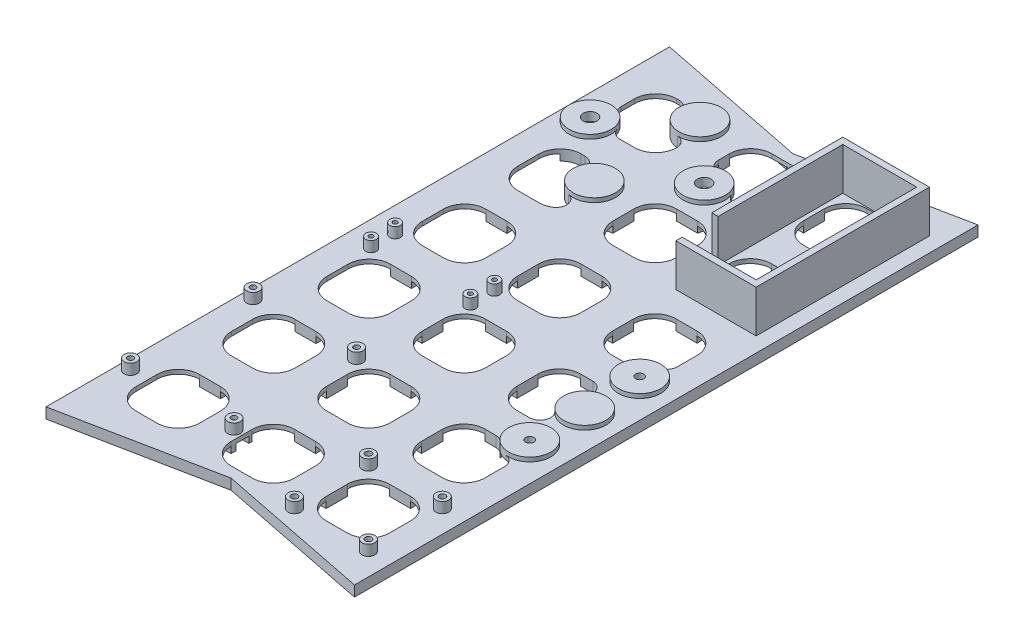
SolidWorks part; units mm, degrees
ref_plane "Front Plane" through (0, 0, 0) normal (0, 0, 1) x (1, 0, 0)
ref_plane "Top Plane" through (0, 0, 0) normal (0, 1, 0) x (1, 0, 0)
ref_plane "Right Plane" through (0, 0, 0) normal (1, 0, 0) x (0, 0, -1)
ref_axis "X" through (-88.99, 0, 0) along (1, 0, 0)
ref_axis "Y" through (0, 55, 0) along (0, -1, 0)
ref_axis "Z" through (0, 0, -88.99) along (0, 0, 1)
sketch "Sketch1" plane through (0, 0, 0) normal (0, 1, 0) x (1, 0, 0)
  line L0 (-75, 150) -> (0, 135) construction
  line L1 (-75, 150) -> (75, 150) construction
  line L2 (-75, 150) -> (-75, -150) construction
  line L3 (-75, -150) -> (75, -150) construction
  line L4 (75, 150) -> (75, -150) construction
  line L5 (-75, 150) -> (75, -150) construction
  line L6 (-75, -150) -> (75, 150) construction
  line L7 (0, 135) -> (75, 150) construction
  line L8 (-75, 0) -> (75, 0) construction
  line L9 (-75, -150) -> (0, -135) construction
  line L10 (0, -135) -> (75, -150) construction
  line L11 (-73, 147.5604) -> (-73, -147.5604)
  line L12 (-73, -147.5604) -> (0, -132.9604)
  line L13 (0, -132.9604) -> (73, -147.5604)
  line L14 (73, 147.5604) -> (73, -147.5604)
  line L15 (0, 132.9604) -> (73, 147.5604)
  line L16 (-73, 147.5604) -> (0, 132.9604)
  point P0 (0, 0)
  dimension "D1" = 300
  dimension "D2" = 150
  dimension "D3" = 15
  dimension "D4" = 2
extrude "Boss-Extrude1" add sketch "Sketch1" along normal blind 2
sketch "Sketch2" plane through (0, 2, 0) normal (0, 1, 0) x (1, 0, 0)
  line L0 (-73, 147.5604) -> (-73, -147.5604) construction
  line L1 (-50, -127.9604) -> (-40, -127.9604)
  line L2 (-60, -117.9604) -> (-60, -107.9604)
  line L3 (-50, -97.9604) -> (-40, -97.9604)
  line L4 (-30, -117.9604) -> (-30, -107.9604)
  line L5 (-15, -117.9604) -> (-15, -107.9604)
  line L6 (-5, -127.9604) -> (5, -127.9604)
  line L7 (15, -117.9604) -> (15, -107.9604)
  line L8 (-5, -97.9604) -> (5, -97.9604)
  line L9 (30, -117.9604) -> (30, -107.9604)
  line L10 (40, -127.9604) -> (50, -127.9604)
  line L11 (60, -117.9604) -> (60, -107.9604)
  line L12 (40, -97.9604) -> (50, -97.9604)
  line L73 (-60, -72.7762) -> (-60, -62.7762)
  line L74 (-50, -82.7762) -> (-40, -82.7762)
  line L75 (-30, -72.7762) -> (-30, -62.7762)
  line L76 (-50, -52.7762) -> (-40, -52.7762)
  line L77 (-15, -72.7762) -> (-15, -62.7762)
  line L78 (-5, -52.7762) -> (5, -52.7762)
  line L79 (15, -72.7762) -> (15, -62.7762)
  line L80 (-5, -82.7762) -> (5, -82.7762)
  line L81 (30, -72.7762) -> (30, -62.7762)
  line L82 (40, -52.7762) -> (50, -52.7762)
  line L83 (60, -72.7762) -> (60, -62.7762)
  line L84 (40, -82.7762) -> (50, -82.7762)
  line L85 (-60, -27.5921) -> (-60, -17.5921)
  line L86 (-50, -37.5921) -> (-40, -37.5921)
  line L87 (-30, -27.5921) -> (-30, -17.5921)
  line L88 (-50, -7.5921) -> (-40, -7.5921)
  line L89 (-15, -27.5921) -> (-15, -17.5921)
  line L90 (-5, -7.5921) -> (5, -7.5921)
  line L91 (15, -27.5921) -> (15, -17.5921)
  line L92 (-5, -37.5921) -> (5, -37.5921)
  line L93 (30, -27.5921) -> (30, -17.5921)
  line L94 (40, -7.5921) -> (50, -7.5921)
  line L95 (60, -27.5921) -> (60, -17.5921)
  line L96 (40, -37.5921) -> (50, -37.5921)
  line L97 (-60, 17.5921) -> (-60, 27.5921)
  line L98 (-50, 7.5921) -> (-40, 7.5921)
  line L99 (-30, 17.5921) -> (-30, 27.5921)
  line L100 (-50, 37.5921) -> (-40, 37.5921)
  line L101 (-15, 17.5921) -> (-15, 27.5921)
  line L102 (-5, 37.5921) -> (5, 37.5921)
  line L103 (15, 17.5921) -> (15, 27.5921)
  line L104 (-5, 7.5921) -> (5, 7.5921)
  line L105 (30, 17.5921) -> (30, 27.5921)
  line L106 (40, 37.5921) -> (50, 37.5921)
  line L107 (60, 17.5921) -> (60, 27.5921)
  line L108 (40, 7.5921) -> (50, 7.5921)
  line L109 (-60, 62.7762) -> (-60, 72.7762)
  line L110 (-50, 52.7762) -> (-40, 52.7762)
  line L111 (-30, 62.7762) -> (-30, 72.7762)
  line L112 (-50, 82.7762) -> (-40, 82.7762)
  line L113 (-15, 62.7762) -> (-15, 72.7762)
  line L114 (-5, 82.7762) -> (5, 82.7762)
  line L115 (15, 62.7762) -> (15, 72.7762)
  line L116 (-5, 52.7762) -> (5, 52.7762)
  line L117 (30, 62.7762) -> (30, 72.7762)
  line L118 (40, 82.7762) -> (50, 82.7762)
  line L119 (60, 62.7762) -> (60, 72.7762)
  line L120 (40, 52.7762) -> (50, 52.7762)
  line L121 (-60, 107.9604) -> (-60, 117.9604)
  line L122 (-50, 97.9604) -> (-40, 97.9604)
  line L123 (-30, 107.9604) -> (-30, 117.9604)
  line L124 (-50, 127.9604) -> (-40, 127.9604)
  line L125 (-15, 107.9604) -> (-15, 117.9604)
  line L126 (-5, 127.9604) -> (5, 127.9604)
  line L127 (15, 107.9604) -> (15, 117.9604)
  line L128 (-5, 97.9604) -> (5, 97.9604)
  line L129 (30, 107.9604) -> (30, 117.9604)
  line L130 (40, 127.9604) -> (50, 127.9604)
  line L131 (60, 107.9604) -> (60, 117.9604)
  line L132 (40, 97.9604) -> (50, 97.9604)
  arc A0 (-60, -117.9604) -> (-50, -127.9604) centre (-50, -117.9604) ccw
  arc A1 (-40, -127.9604) -> (-30, -117.9604) centre (-40, -117.9604) ccw
  arc A2 (-30, -107.9604) -> (-40, -97.9604) centre (-40, -107.9604) ccw
  arc A3 (-50, -97.9604) -> (-60, -107.9604) centre (-50, -107.9604) ccw
  arc A4 (60, -107.9604) -> (50, -97.9604) centre (50, -107.9604) ccw
  arc A5 (50, -127.9604) -> (60, -117.9604) centre (50, -117.9604) ccw
  arc A6 (40, -127.9604) -> (30, -117.9604) centre (40, -117.9604) cw
  arc A7 (30, -107.9604) -> (40, -97.9604) centre (40, -107.9604) cw
  arc A8 (-15, -107.9604) -> (-5, -97.9604) centre (-5, -107.9604) cw
  arc A9 (-15, -117.9604) -> (-5, -127.9604) centre (-5, -117.9604) ccw
  arc A10 (15, -117.9604) -> (5, -127.9604) centre (5, -117.9604) cw
  arc A11 (15, -107.9604) -> (5, -97.9604) centre (5, -107.9604) ccw
  arc A12 (-50, -52.7762) -> (-60, -62.7762) centre (-50, -62.7762) ccw
  arc A13 (-60, -72.7762) -> (-50, -82.7762) centre (-50, -72.7762) ccw
  arc A14 (-40, -82.7762) -> (-30, -72.7762) centre (-40, -72.7762) ccw
  arc A15 (-30, -62.7762) -> (-40, -52.7762) centre (-40, -62.7762) ccw
  arc A16 (-15, -72.7762) -> (-5, -82.7762) centre (-5, -72.7762) ccw
  arc A17 (-15, -62.7762) -> (-5, -52.7762) centre (-5, -62.7762) cw
  arc A18 (15, -62.7762) -> (5, -52.7762) centre (5, -62.7762) ccw
  arc A19 (15, -72.7762) -> (5, -82.7762) centre (5, -72.7762) cw
  arc A20 (30, -62.7762) -> (40, -52.7762) centre (40, -62.7762) cw
  arc A21 (40, -82.7762) -> (30, -72.7762) centre (40, -72.7762) cw
  arc A22 (60, -62.7762) -> (50, -52.7762) centre (50, -62.7762) ccw
  arc A23 (50, -82.7762) -> (60, -72.7762) centre (50, -72.7762) ccw
  arc A24 (-50, -7.5921) -> (-60, -17.5921) centre (-50, -17.5921) ccw
  arc A25 (-60, -27.5921) -> (-50, -37.5921) centre (-50, -27.5921) ccw
  arc A26 (-40, -37.5921) -> (-30, -27.5921) centre (-40, -27.5921) ccw
  arc A27 (-30, -17.5921) -> (-40, -7.5921) centre (-40, -17.5921) ccw
  arc A28 (-15, -27.5921) -> (-5, -37.5921) centre (-5, -27.5921) ccw
  arc A29 (-15, -17.5921) -> (-5, -7.5921) centre (-5, -17.5921) cw
  arc A30 (15, -17.5921) -> (5, -7.5921) centre (5, -17.5921) ccw
  arc A31 (15, -27.5921) -> (5, -37.5921) centre (5, -27.5921) cw
  arc A32 (30, -17.5921) -> (40, -7.5921) centre (40, -17.5921) cw
  arc A33 (40, -37.5921) -> (30, -27.5921) centre (40, -27.5921) cw
  arc A34 (60, -17.5921) -> (50, -7.5921) centre (50, -17.5921) ccw
  arc A35 (50, -37.5921) -> (60, -27.5921) centre (50, -27.5921) ccw
  arc A36 (-50, 37.5921) -> (-60, 27.5921) centre (-50, 27.5921) ccw
  arc A37 (-60, 17.5921) -> (-50, 7.5921) centre (-50, 17.5921) ccw
  arc A38 (-40, 7.5921) -> (-30, 17.5921) centre (-40, 17.5921) ccw
  arc A39 (-30, 27.5921) -> (-40, 37.5921) centre (-40, 27.5921) ccw
  arc A40 (-15, 17.5921) -> (-5, 7.5921) centre (-5, 17.5921) ccw
  arc A41 (-15, 27.5921) -> (-5, 37.5921) centre (-5, 27.5921) cw
  arc A42 (15, 27.5921) -> (5, 37.5921) centre (5, 27.5921) ccw
  arc A43 (15, 17.5921) -> (5, 7.5921) centre (5, 17.5921) cw
  arc A44 (30, 27.5921) -> (40, 37.5921) centre (40, 27.5921) cw
  arc A45 (40, 7.5921) -> (30, 17.5921) centre (40, 17.5921) cw
  arc A46 (60, 27.5921) -> (50, 37.5921) centre (50, 27.5921) ccw
  arc A47 (50, 7.5921) -> (60, 17.5921) centre (50, 17.5921) ccw
  arc A48 (-50, 82.7762) -> (-60, 72.7762) centre (-50, 72.7762) ccw
  arc A49 (-60, 62.7762) -> (-50, 52.7762) centre (-50, 62.7762) ccw
  arc A50 (-40, 52.7762) -> (-30, 62.7762) centre (-40, 62.7762) ccw
  arc A51 (-30, 72.7762) -> (-40, 82.7762) centre (-40, 72.7762) ccw
  arc A52 (-15, 62.7762) -> (-5, 52.7762) centre (-5, 62.7762) ccw
  arc A53 (-15, 72.7762) -> (-5, 82.7762) centre (-5, 72.7762) cw
  arc A54 (15, 72.7762) -> (5, 82.7762) centre (5, 72.7762) ccw
  arc A55 (15, 62.7762) -> (5, 52.7762) centre (5, 62.7762) cw
  arc A56 (30, 72.7762) -> (40, 82.7762) centre (40, 72.7762) cw
  arc A57 (40, 52.7762) -> (30, 62.7762) centre (40, 62.7762) cw
  arc A58 (60, 72.7762) -> (50, 82.7762) centre (50, 72.7762) ccw
  arc A59 (50, 52.7762) -> (60, 62.7762) centre (50, 62.7762) ccw
  arc A60 (-50, 127.9604) -> (-60, 117.9604) centre (-50, 117.9604) ccw
  arc A61 (-60, 107.9604) -> (-50, 97.9604) centre (-50, 107.9604) ccw
  arc A62 (-40, 97.9604) -> (-30, 107.9604) centre (-40, 107.9604) ccw
  arc A63 (-30, 117.9604) -> (-40, 127.9604) centre (-40, 117.9604) ccw
  arc A64 (-15, 107.9604) -> (-5, 97.9604) centre (-5, 107.9604) ccw
  arc A65 (-15, 117.9604) -> (-5, 127.9604) centre (-5, 117.9604) cw
  arc A66 (15, 117.9604) -> (5, 127.9604) centre (5, 117.9604) ccw
  arc A67 (15, 107.9604) -> (5, 97.9604) centre (5, 107.9604) cw
  arc A68 (30, 117.9604) -> (40, 127.9604) centre (40, 117.9604) cw
  arc A69 (40, 97.9604) -> (30, 107.9604) centre (40, 107.9604) cw
  arc A70 (60, 117.9604) -> (50, 127.9604) centre (50, 117.9604) ccw
  arc A71 (50, 97.9604) -> (60, 107.9604) centre (50, 107.9604) ccw
  point P81 (-30, -127.9604)
  point P84 (-30, -97.9604)
  point P87 (-60, -97.9604)
  dimension "D9" = 10
  dimension "D7" = 10
  dimension "D1" = 30
  dimension "D2" = 30
  dimension "D3" = 13
  dimension "D4" = 5
  dimension "D6" = 15
  dimension "D8" = 6
  dimension "D10" = 5
  dimension "D5" = 3
extrude "Cut-Extrude1" cut sketch "Sketch2" against normal through all
sketch "Sketch3" plane through (0, 2, 0) normal (0, 1, 0) x (1, 0, 0)
  line L1 (-73, 147.5604) -> (-73, -147.5604) construction
  circle A0 centre (-68, -54.5604) radius 3
  circle A1 centre (-19, -54.5604) radius 3
  circle A2 centre (-68, -112.5604) radius 3
  circle A3 centre (-19, -112.5604) radius 3
  dimension "D1" = 6
  dimension "D2" = 49
  dimension "D3" = 58
  dimension "D4" = 5
  dimension "D5" = 35
extrude "Boss-Extrude2" add sketch "Sketch3" along normal blind 5 and the other way through all
sketch "Sketch4" plane through (0, 7, 0) normal (0, 1, 0) x (1, 0, 0)
  circle A1 centre (-19, -112.5604) radius 1.35
  circle A2 centre (-68, -112.5604) radius 1.35
  circle A3 centre (-68, -54.5604) radius 1.35
  circle A4 centre (-19, -54.5604) radius 1.35
  dimension "D1" = 2.7
extrude "Cut-Extrude2" cut sketch "Sketch4" against normal through all
sketch "Sketch5" plane through (0, 2, 0) normal (0, 1, 0) x (1, 0, 0)
  line L0 (30, -112.9604) -> (60, -112.9604) construction
  line L1 (30, -107.9604) -> (30, -117.9604) construction
  line L2 (60, -117.9604) -> (60, -107.9604) construction
  circle A0 centre (27.5, -95.4604) radius 3
  circle A2 centre (62.5, -95.4604) radius 3
  circle A4 centre (62.5, -130.4604) radius 3
  circle A6 centre (27.5, -130.4604) radius 3
  circle A9 centre (45, -112.9604) radius 24.7487 construction
  dimension "D2" = 6
  dimension "D3" = 35
  dimension "D4" = 35
extrude "Boss-Extrude3" add sketch "Sketch5" along normal blind 5
sketch "Sketch6" plane through (0, 7, 0) normal (0, 1, 0) x (1, 0, 0)
  circle A0 centre (27.5, -95.4604) radius 1.5
  circle A1 centre (62.5, -95.4604) radius 1.5
  circle A2 centre (62.5, -130.4604) radius 1.5
  circle A3 centre (27.5, -130.4604) radius 1.5
  dimension "D1" = 3
extrude "Cut-Extrude3" cut sketch "Sketch6" against normal through all
sketch "Sketch7" plane through (0, 2, 0) normal (0, 1, 0) x (1, 0, 0)
  line L0 (73, -147.5604) -> (73, 147.5604) construction
  line L1 (30, -22.5921) -> (73, -22.5921) construction
  line L2 (30, -17.5921) -> (30, -27.5921) construction
  line L3 (57, 3.4079) -> (57, -48.5921) construction
  circle A0 centre (57, -48.5921) radius 10
  circle A1 centre (57, 3.4079) radius 10
  circle A2 centre (57, -22.5921) radius 10
  point P6 (51.5, -22.5921)
  point P13 (57, -22.5921)
  dimension "D1" = 20
  dimension "D2" = 16
  dimension "D3" = 52
extrude "Boss-Extrude4" add sketch "Sketch7" along normal blind 2 and the other way through all
sketch "Sketch8" plane through (0, 4, 0) normal (0, 1, 0) x (1, 0, 0)
  circle A0 centre (57, 3.4079) radius 1.95
  circle A1 centre (57, -48.5921) radius 1.95
  dimension "D1" = 3.9
extrude "Cut-Extrude4" cut sketch "Sketch8" against normal through all
sketch "Sketch9" plane through (0, 2, 0) normal (0, 1, 0) x (1, 0, 0)
  line L0 (73, 0) -> (-73, 0) construction
  line L1 (73, -147.5604) -> (73, 147.5604) construction
  line L2 (-73, 147.5604) -> (-73, -147.5604) construction
  line L3 (-61, 5.7) -> (-61, -5.7) construction
  circle A0 centre (-61, 5.7) radius 2.5
  circle A1 centre (-61, -5.7) radius 2.5
  circle A2 centre (-14, -5.7) radius 2.5
  circle A3 centre (-14, 5.7) radius 2.5
  point P14 (-61, 0)
  dimension "D1" = 5
  dimension "D4" = 12
  dimension "D2" = 11.4
  dimension "D3" = 47
extrude "Boss-Extrude5" add sketch "Sketch9" along normal blind 5
sketch "Sketch10" plane through (0, 7, 0) normal (0, 1, 0) x (1, 0, 0)
  circle A0 centre (-14, 5.7) radius 1.05
  circle A1 centre (-14, -5.7) radius 1.05
  circle A2 centre (-61, -5.7) radius 1.05
  circle A3 centre (-61, 5.7) radius 1.05
  dimension "D1" = 2.1
extrude "Cut-Extrude5" cut sketch "Sketch10" against normal through all
sketch "Sketch11" plane through (0, 2, 0) normal (0, 1, 0) x (1, 0, 0)
  line L0 (-73, 147.5604) -> (-73, -147.5604) construction
  line L1 (-34, 122.9604) -> (-34, 72.9604) construction
  line L2 (-61, 97.9604) -> (-7, 97.9604) construction
  circle A3 centre (-7, 97.9604) radius 10
  circle A4 centre (-61, 97.9604) radius 10
  circle A5 centre (-34, 122.9604) radius 10
  circle A6 centre (-34, 72.9604) radius 10
  point P11 (-34, 97.9604)
  dimension "D1" = 20
  dimension "D2" = 54
  dimension "D3" = 35
  dimension "D4" = 12
  dimension "D5" = 50
extrude "Boss-Extrude6" add sketch "Sketch11" along normal blind 2 and the other way through all
sketch "Sketch12" plane through (0, 4, 0) normal (0, 1, 0) x (1, 0, 0)
  circle A0 centre (-61, 97.9604) radius 3.25
  circle A1 centre (-7, 97.9604) radius 3.25
  dimension "D1" = 6.5
extrude "Cut-Extrude6" cut sketch "Sketch12" against normal through all
sketch "Sketch13" plane through (0, 2, 0) normal (0, 1, 0) x (1, 0, 0)
  line L0 (28, 49.5604) -> (66, 49.5604)
  line L1 (66, 49.5604) -> (66, 131.5604)
  line L2 (66, 131.5604) -> (25, 131.5604)
  line L3 (25, 131.5604) -> (25, 69.5604)
  line L4 (25, 69.5604) -> (28, 69.5604)
  line L5 (28, 69.5604) -> (28, 128.5604)
  line L6 (28, 128.5604) -> (63, 128.5604)
  line L7 (63, 128.5604) -> (63, 52.5604)
  line L8 (63, 52.5604) -> (28, 52.5604)
  line L9 (28, 52.5604) -> (28, 49.5604)
  line L10 (73, -147.5604) -> (73, 147.5604) construction
  dimension "D1" = 62
  dimension "D2" = 3
  dimension "D3" = 3
  dimension "D4" = 3
  dimension "D5" = 3
  dimension "D6" = 35
  dimension "D7" = 76
  dimension "D8" = 16
  dimension "D9" = 7
extrude "Boss-Extrude7" add sketch "Sketch13" along normal blind 20 and the other way through all
fillet "Fillet2" radius 5 14 edges at (58.9879, 1, -13.2083) (47.9174, 1, -7.5921) (47.9174, 1, 52.7762) (58.9879, 1, 58.3925) (58.7473, 1, 32.4382) (58.7473, 1, 12.7459) (-30, 1, -63.7952) (-37.2926, 1, -82.4028) (-14.4353, 1, -104.6474) (3, 1, -97.9604) (-59.9999, 1, -107.9103) (-51.0001, 1, -98.0105) (-42.6603, 1, -127.9604) (-30, 1, -113.7952)
sketch "Sketch15" plane through (0, 0, 0) normal (0, -1, 0) x (1, 0, 0)
  line L0 (0, 132.9604) -> (73, 147.5604) construction
  line L1 (-73, 147.5604) -> (0, 132.9604) construction
  line L2 (73, 147.5604) -> (73, -147.5604) construction
  line L3 (73, -147.5604) -> (0, -132.9604) construction
  line L4 (0, -132.9604) -> (-73, -147.5604) construction
  line L5 (-73, -147.5604) -> (-73, 147.5604) construction
  line L6 (0, 132.9604) -> (73, 147.5604)
  line L7 (-73, 147.5604) -> (0, 132.9604)
  line L8 (73, 147.5604) -> (73, -147.5604)
  line L9 (73, -147.5604) -> (0, -132.9604)
  line L10 (0, -132.9604) -> (-73, -147.5604)
  line L11 (-73, -147.5604) -> (-73, 147.5604)
  line L12 (0, 129.901) -> (70, 143.901)
  line L13 (70, 143.901) -> (70, -143.901)
  line L14 (70, -143.901) -> (0, -129.901)
  line L15 (0, -129.901) -> (-70, -143.901)
  line L16 (-70, -143.901) -> (-70, 143.901)
  line L17 (-70, 143.901) -> (0, 129.901)
  dimension "D1" = 3
extrude "Boss-Extrude9" add sketch "Sketch15" along normal blind 3
sketch "Sketch16" plane through (0, 0, 0) normal (0, -1, 0) x (1, 0, 0)
  line L0 (-50, 37.5921) -> (-40, 37.5921) construction
  line L1 (40, 97.9604) -> (50, 97.9604)
  line L2 (40, 97.9604) -> (40, 82.7762)
  line L3 (40, 82.7762) -> (50, 82.7762)
  line L4 (50, 97.9604) -> (50, 82.7762)
  line L5 (-50, 97.9604) -> (-40, 97.9604)
  line L6 (-50, 97.9604) -> (-50, 82.7762)
  line L7 (-50, 82.7762) -> (-40, 82.7762)
  line L8 (-40, 97.9604) -> (-40, 82.7762)
  line L9 (-5, 97.9604) -> (5, 97.9604)
  line L10 (-5, 97.9604) -> (-5, 82.7762)
  line L11 (-5, 82.7762) -> (5, 82.7762)
  line L12 (5, 97.9604) -> (5, 82.7762)
  line L13 (30, 62.7762) -> (15, 62.7762)
  line L14 (30, 62.7762) -> (30, 72.7762)
  line L15 (30, 72.7762) -> (15, 72.7762)
  line L16 (15, 62.7762) -> (15, 72.7762)
  line L17 (-15, 62.7762) -> (-30, 62.7762)
  line L18 (-15, 62.7762) -> (-15, 72.7762)
  line L19 (-15, 72.7762) -> (-30, 72.7762)
  line L20 (-30, 62.7762) -> (-30, 72.7762)
  line L21 (-50, 52.7762) -> (-40, 52.7762)
  line L22 (-50, 52.7762) -> (-50, 37.5921)
  line L23 (-50, 37.5921) -> (-40, 37.5921)
  line L24 (-40, 52.7762) -> (-40, 37.5921)
  line L25 (-5, -82.7762) -> (5, -82.7762)
  line L26 (-5, 52.7762) -> (5, 52.7762)
  line L27 (-5, 52.7762) -> (-5, 37.5921)
  line L28 (-5, 37.5921) -> (5, 37.5921)
  line L29 (5, 52.7762) -> (5, 37.5921)
  line L33 (40, 37.5921) -> (40, 52.7762)
  line L35 (40, 7.5921) -> (40, -7.5921)
  line L38 (-5, 7.5921) -> (5, 7.5921)
  line L39 (-5, 7.5921) -> (-5, -7.5921)
  line L40 (-5, -7.5921) -> (5, -7.5921)
  line L41 (5, 7.5921) -> (5, -7.5921)
  line L42 (30, 17.5921) -> (15, 17.5921)
  line L43 (30, 17.5921) -> (30, 27.5921)
  line L44 (30, 27.5921) -> (15, 27.5921)
  line L45 (15, 17.5921) -> (15, 27.5921)
  line L46 (-15, 27.5921) -> (-30, 27.5921)
  line L47 (-15, 27.5921) -> (-15, 17.5921)
  line L48 (-15, 17.5921) -> (-30, 17.5921)
  line L49 (-30, 27.5921) -> (-30, 17.5921)
  line L50 (-40, 7.5921) -> (-50, 7.5921)
  line L51 (-40, 7.5921) -> (-40, -7.5921)
  line L52 (-40, -7.5921) -> (-50, -7.5921)
  line L53 (-50, 7.5921) -> (-50, -7.5921)
  line L54 (-30, -17.5921) -> (-15, -17.5921)
  line L55 (-30, -17.5921) -> (-30, -27.5921)
  line L56 (-30, -27.5921) -> (-15, -27.5921)
  line L57 (-15, -17.5921) -> (-15, -27.5921)
  line L58 (15, -17.5921) -> (30, -17.5921)
  line L59 (15, -17.5921) -> (15, -27.5921)
  line L60 (15, -27.5921) -> (30, -27.5921)
  line L61 (30, -17.5921) -> (30, -27.5921)
  line L66 (-50, -37.5921) -> (-40, -37.5921)
  line L67 (-50, -37.5921) -> (-50, -52.7762)
  line L68 (-50, -52.7762) -> (-40, -52.7762)
  line L69 (-40, -37.5921) -> (-40, -52.7762)
  line L70 (-5, -37.5921) -> (5, -37.5921)
  line L71 (-5, -37.5921) -> (-5, -52.7762)
  line L72 (-5, -52.7762) -> (5, -52.7762)
  line L73 (5, -37.5921) -> (5, -52.7762)
  line L74 (40, -37.5921) -> (50, -37.5921)
  line L75 (40, -37.5921) -> (40, -52.7762)
  line L76 (40, -52.7762) -> (50, -52.7762)
  line L77 (50, -37.5921) -> (50, -52.7762)
  line L78 (30, -62.7762) -> (15, -62.7762)
  line L79 (30, -62.7762) -> (30, -72.7762)
  line L80 (30, -72.7762) -> (15, -72.7762)
  line L81 (15, -62.7762) -> (15, -72.7762)
  line L82 (15, -107.9604) -> (30, -107.9604)
  line L83 (15, -107.9604) -> (15, -117.9604)
  line L84 (15, -117.9604) -> (30, -117.9604)
  line L85 (30, -107.9604) -> (30, -117.9604)
  line L86 (40, -82.7762) -> (50, -82.7762)
  line L87 (40, -82.7762) -> (40, -97.9604)
  line L88 (40, -97.9604) -> (50, -97.9604)
  line L89 (50, -82.7762) -> (50, -97.9604)
  line L92 (-15, -117.9604) -> (-15, -112.6573)
  line L93 (-15, -117.9604) -> (-15, -112.6573) construction
  line L94 (-15, -112.6573) -> (-33.1969, -112.6573)
  line L96 (-40, -97.9604) -> (-46.8579, -97.9604)
  line L100 (-15, -62.7762) -> (-15, -72.7762)
  line L102 (-32.6315, -59.0482) -> (-15, -62.7762)
  line L105 (-15, 107.9604) -> (-30, 107.9604)
  line L106 (15, 117.9604) -> (30, 117.9604)
  line L107 (15, 117.9604) -> (15, 107.9604)
  line L108 (15, 107.9604) -> (30, 107.9604)
  line L109 (30, 117.9604) -> (30, 107.9604)
  line L110 (-30, 107.9604) -> (-30, 117.9604)
  line L111 (-30, 117.9604) -> (-15, 117.9604)
  line L112 (-15, 107.9604) -> (-15, 117.9604) construction
  line L113 (-15, 117.9604) -> (-15, 115.5604)
  line L114 (-15, 115.5604) -> (-22, 115.5604)
  line L115 (-22, 115.5604) -> (-22, 109.5604)
  line L116 (-22, 109.5604) -> (-15, 109.5604)
  line L117 (-15, 109.5604) -> (-15, 107.9604)
  line L118 (-15, -117.9604) -> (-42.6603, -117.9604)
  line L119 (-5, -82.7762) -> (2.3262, -101.5689)
  line L120 (5, -82.7762) -> (8.9787, -98.786)
  line L121 (-46.8579, -97.9604) -> (-57.0711, -79.8473)
  line L122 (-40, -97.9604) -> (-44.1423, -80.6894)
  line L123 (-48.2059, -82.7762) -> (-50, -82.7762) construction
  line L124 (-48.2059, -82.7762) -> (-50, -82.7762)
  line L125 (-15, -72.7762) -> (-43.9983, -72.7762)
  line L126 (49.0936, -9.5307) -> (49.0936, 8.813)
  line L128 (40, -7.5921) -> (45.1404, -7.5921) construction
  line L129 (45.8197, 7.5921) -> (40, 7.5921) construction
  line L130 (45.8197, 7.5921) -> (40, 7.5921)
  line L131 (40, -7.5921) -> (45.1404, -7.5921)
  line L132 (50.384, 34.6333) -> (50.384, 56.0907)
  line L133 (40, 37.5921) -> (45.8197, 37.5921) construction
  line L134 (45.1404, 52.7762) -> (40, 52.7762) construction
  line L135 (40, 37.5921) -> (45.8197, 37.5921)
  line L136 (45.1404, 52.7762) -> (40, 52.7762)
  arc A0 (-30, 27.5921) -> (-40, 37.5921) centre (-40, 27.5921) ccw construction
  arc A1 (-15, 17.5921) -> (-5, 7.5921) centre (-5, 17.5921) ccw construction
  arc A2 (30, 17.5921) -> (40, 7.5921) centre (40, 17.5921) ccw construction
  arc A3 (49.0936, -9.5307) -> (45.1404, -7.5921) centre (45.1404, -12.5921) ccw construction
  arc A4 (45.8197, 7.5921) -> (49.0936, 8.813) centre (45.8197, 12.5921) ccw
  arc A5 (49.0936, -9.5307) -> (45.1404, -7.5921) centre (45.1404, -12.5921) ccw
  arc A6 (-15, -117.9604) -> (-5, -127.9604) centre (-5, -117.9604) ccw construction
  arc A7 (-34.6667, -112.9826) -> (-30, -107.9938) centre (-35, -107.9938) ccw construction
  arc A8 (-36.3925, -63.2508) -> (-35.1776, -54.0158) centre (-37.5888, -58.396) ccw construction
  circle A11 centre (-19, 112.5604) radius 1.35 construction
  arc A12 (-34.6667, -112.9826) -> (-44, -122.9604) centre (-34, -122.9604) ccw construction
  arc A13 (-34.6667, -112.9826) -> (-33.1969, -112.6573) centre (-35, -107.9938) ccw
  arc A14 (-34.6667, -112.9826) -> (-42.6603, -117.9604) centre (-34, -122.9604) ccw
  arc A15 (8.9787, -98.786) -> (2.3262, -101.5689) centre (6.9893, -103.3732) ccw construction
  arc A16 (8.9787, -98.786) -> (2.3262, -101.5689) centre (6.9893, -103.3732) ccw
  arc A17 (-60, -72.7762) -> (-50, -82.7762) centre (-50, -72.7762) ccw construction
  arc A18 (-48.2059, -82.7762) -> (-43.4706, -76.171) centre (-48.2059, -77.7762) ccw construction
  arc A19 (-48.2059, -82.7762) -> (-44.1423, -80.6894) centre (-48.2059, -77.7762) ccw
  arc A20 (-57.0711, -79.8473) -> (-50, -82.7762) centre (-50, -72.7762) ccw
  arc A21 (-36.3925, -63.2508) -> (-43.4706, -76.171) centre (-34, -72.9604) ccw construction
  arc A22 (-36.3925, -63.2508) -> (-32.6315, -59.0482) centre (-37.5888, -58.396) ccw
  arc A23 (-36.3925, -63.2508) -> (-43.9983, -72.7762) centre (-34, -72.9604) ccw
  arc A24 (45.8197, 7.5921) -> (49.5464, 15.9254) centre (45.8197, 12.5921) ccw construction
  arc A25 (49.5464, 29.2587) -> (45.8197, 37.5921) centre (45.8197, 32.5921) ccw construction
  arc A26 (55.6667, 58.5028) -> (49.0936, 54.7148) centre (57, 48.5921) ccw construction
  arc A27 (45.1404, 52.7762) -> (49.0936, 54.7148) centre (45.1404, 57.7762) ccw construction
  arc A28 (50.384, 34.6333) -> (45.8197, 37.5921) centre (45.8197, 32.5921) ccw
  arc A29 (50.384, 56.0907) -> (49.0936, 54.7148) centre (57, 48.5921) ccw
  arc A30 (45.1404, 52.7762) -> (49.0936, 54.7148) centre (45.1404, 57.7762) ccw
  point P212 (52.7704, 57.6536)
  point P213 (40, 35.2418)
  dimension "D2" = 3
  dimension "D1" = 3
  dimension "D3" = 3
extrude "Boss-Extrude10" add sketch "Sketch16" along normal up to surface (3 mm away) up to face at (0, -3, 0)
